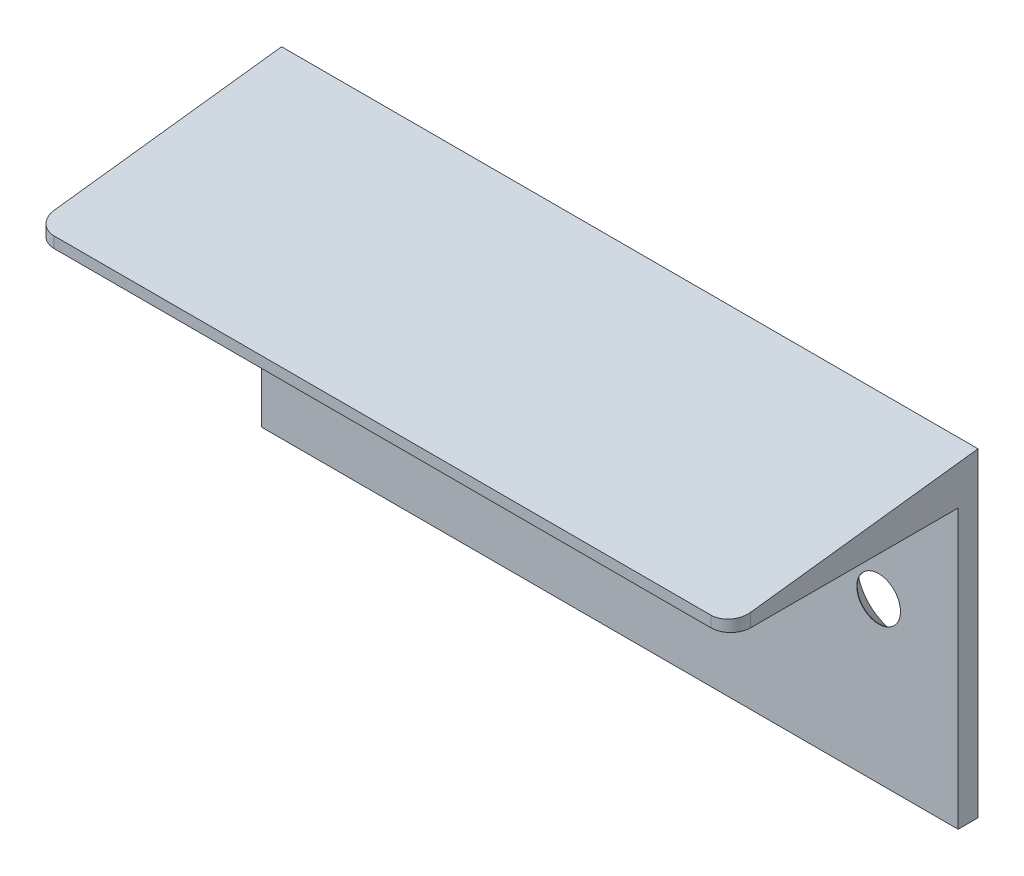
SolidWorks part; units mm, degrees
material "6061 Alloy"
ref_plane "Top Plane" through (0, 0, 0) normal (0, 0, 1) x (1, 0, 0)
ref_plane "Front Plane" through (0, 0, 0) normal (0, 1, 0) x (1, 0, 0)
ref_plane "Right Plane" through (0, 0, 0) normal (1, 0, 0) x (0, 0, -1)
sketch "Sketch1" plane through (0, 0, 0) normal (0, 0, 1) x (1, 0, 0)
  line L1 (-43.8, -20.1) -> (43.8, -20.1)
  line L2 (-43.8, -20.1) -> (-43.8, 20.1)
  line L3 (-43.8, 20.1) -> (43.8, 20.1)
  line L4 (43.8, -20.1) -> (43.8, 20.1)
  line L5 (-43.8, -20.1) -> (43.8, 20.1) construction
  line L6 (-43.8, 20.1) -> (43.8, -20.1) construction
  point P0 (0, 0)
  dimension "D1" = 40.2
  dimension "D2" = 87.6
extrude "Boss-Extrude1" add sketch "Sketch1" along normal blind 2.5
sketch "Sketch3" plane through (0, 0, 2.5) normal (0, 0, 1) x (1, 0, 0)
  line L0 (43.8, -20.1) -> (43.8, 20.1) construction
  line L1 (-43.8, 20.1) -> (43.8, 20.1)
  line L2 (-43.8, 20.1) -> (-43.8, 14.9)
  line L3 (-43.8, 14.9) -> (43.8, 14.9)
  line L4 (43.8, 20.1) -> (43.8, 14.9)
  dimension "D1" = 5.2
extrude "Boss-Extrude2" add sketch "Sketch3" along normal blind 28.599
fillet "Fillet1" radius 2.5 2 edges at (-43.8, 17.5, 31.099) (43.8, 17.5, 31.099)
sketch "Sketch4" plane through (0, 20.1, 0) normal (0, 1, 0) x (1, 0, 0)
  line L0 (43.8, 0) -> (-43.8, 0) construction
  line L1 (-43.8, 0) -> (43.8, 0)
  line L2 (-43.8, 0) -> (-43.8, -37.3428)
  line L3 (-43.8, -37.3428) -> (43.8, -37.3428)
  line L4 (43.8, 0) -> (43.8, -37.3428)
  line L5 (-43.8, -28.599) -> (-43.8, 0) construction
revolve "Cut-Revolve2" cut sketch "Sketch4" angle 7 about L1
hole_wizard "CSK for M5 Flat Head Machine Screw1" positions "Sketch5" profile "Sketch6" countersink size "M5" standard "ANSI Metric"
sketch "Sketch5" plane through (0, 0, 0) normal (0, 0, -1) x (-1, 0, 0)
  line L0 (-43.8, -20.1) -> (-43.8, 20.1) construction
  line L1 (43.8, 20.1) -> (43.8, -20.1) construction
  line L2 (-43.8, 20.1) -> (43.8, 20.1) construction
  point P0 (-33.8, 0)
  point P2 (33.8, 0)
  dimension "D1" = 10
  dimension "D2" = 10
  dimension "D3" = 20.1
  dimension "D4" = 20.1
sketch "Sketch6" plane through (33.8, 0, 0) normal (1, 0, 0) x (0, 1, 0)
  line L0 (0, 0) -> (0, 14.0524)
  line L1 (0, 14.0524) -> (2.75, 12.4)
  line L2 (2.75, 12.4) -> (2.75, 2.45)
  line L3 (2.75, 2.45) -> (5.2, 0)
  line L5 (5.2, 0) -> (0, 0)
  line L6 (-2.75, 2.45) -> (-5.2, 0) construction
  line L10 (0, 14.0524) -> (-2.75, 12.4) construction
  line L11 (0, -6.35) -> (0, 107.95) construction
  dimension "Hole Dia." = 5.5
  dimension "Hole Depth" = 12.4
  dimension "Near C'Sink Dia." = 10.4
  dimension "Near C'Sink Angle" = 90
  dimension "Drill Angle" = 118
